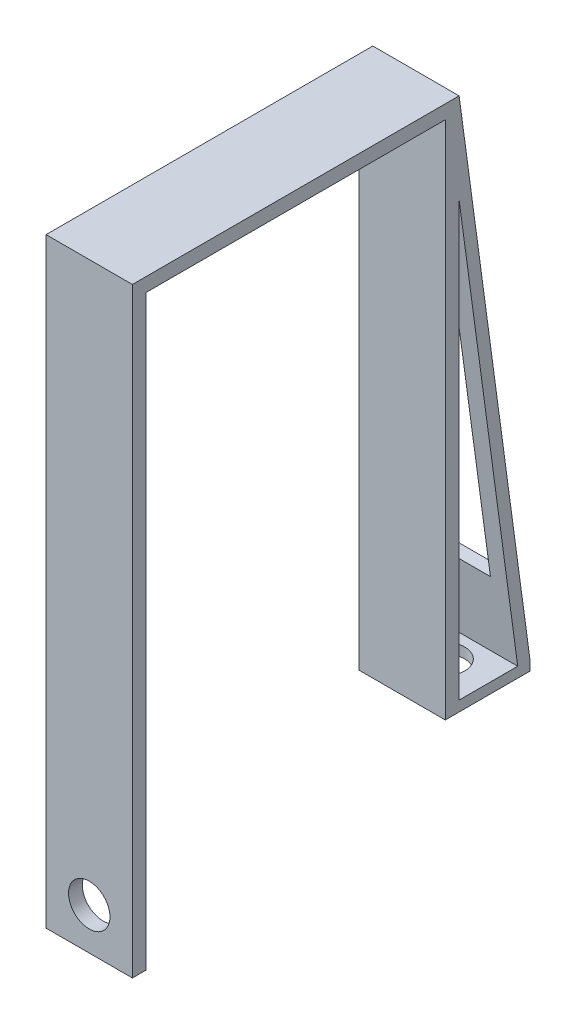
SolidWorks part; units mm, degrees
ref_plane "Front Plane" through (0, 0, 0) normal (0, 0, 1) x (1, 0, 0)
ref_plane "Top Plane" through (0, 0, 0) normal (0, 1, 0) x (1, 0, 0)
ref_plane "Right Plane" through (0, 0, 0) normal (1, 0, 0) x (0, 0, -1)
sketch "Sketch2" plane through (0, 0, 0) normal (0, 0, 1) x (1, 0, 0)
  line L1 (-123.2034, -97.4239) -> (-98.2034, -97.4239)
  line L2 (-123.2034, -97.4239) -> (-123.2034, 72.5761)
  line L3 (-123.2034, 72.5761) -> (-98.2034, 72.5761)
  line L4 (-98.2034, -97.4239) -> (-98.2034, 72.5761)
  circle A2 centre (-110.7034, -85.3746) radius 6
  dimension "D1" = 170
  dimension "D2" = 25
extrude "Boss-Extrude1" add sketch "Sketch2" along normal blind 4
sketch "Sketch3" plane through (0, 72.5761, 0) normal (0, 1, 0) x (1, 0, 0)
  line L13 (-123.2034, -4) -> (-98.2034, -4)
  line L14 (-123.2034, -4) -> (-123.2034, 86.65)
  line L15 (-123.2034, 86.65) -> (-98.2034, 86.65)
  line L16 (-98.2034, -4) -> (-98.2034, 86.65)
  dimension "D1" = 25
  dimension "D2" = 90.65
extrude "Boss-Extrude2" add sketch "Sketch3" along normal blind 4
sketch "Sketch5" plane through (0, 0, -86.65) normal (0, 0, -1) x (-1, 0, 0)
  line L9 (98.2034, -78.0239) -> (123.2034, -78.0239)
  line L10 (98.2034, -78.0239) -> (98.2034, 76.5761)
  line L11 (98.2034, 76.5761) -> (123.2034, 76.5761)
  line L12 (123.2034, -78.0239) -> (123.2034, 76.5761)
  dimension "D1" = 25
  dimension "D2" = 154.6
extrude "Boss-Extrude3" add sketch "Sketch5" along normal blind 4 contours L10 L9 L12 L11
sketch "Sketch6" plane through (-123.2034, 0, 0) normal (-1, 0, 0) x (0, 0, 1)
  line L1 (-90.65, -78.0239) -> (-111.1634, -78.0239)
  line L2 (-90.65, -78.0239) -> (-90.65, -75.0239)
  line L3 (-90.65, -75.0239) -> (-111.1634, -75.0239)
  line L4 (-111.1634, -78.0239) -> (-111.1634, -75.0239)
  dimension "D1" = 3
extrude "Boss-Extrude4" add sketch "Sketch6" along direction (-1, 0, 0) on the side against the normal up to surface (25 mm away) up to face at (-98.2034, -6.5739, -43.325)
sketch "Sketch8" plane through (-98.2034, 0, 0) normal (1, 0, 0) x (0, 0, -1)
  line L0 (90.65, 76.5761) -> (111.1634, -75.0239)
  line L1 (111.1634, -75.0239) -> (107.6315, -75.0239)
  line L2 (111.1634, -75.0239) -> (90.65, -75.0239) construction
  line L3 (107.6315, -75.0239) -> (90.65, 50.4744)
  line L4 (90.65, 50.4744) -> (90.65, 76.5761)
  line L5 (90.65, -75.0239) -> (90.65, 76.5761) construction
  dimension "D1" = 3.5
extrude "Boss-Extrude6" add sketch "Sketch8" against normal up to surface (25 mm away) up to face at (-123.2034, -20.2639, -56.8927)
sketch "Sketch12" plane through (0, -78.0239, 0) normal (0, -1, 0) x (-1, 0, 0)
  circle A1 centre (110.7034, 98.7817) radius 6
extrude "Cut-Extrude2" cut sketch "Sketch12" against normal blind 4
sketch "Sketch13" plane through (0, 12.9531, -95.7271) normal (0, -0.1341, 0.991) x (1, 0, 0)
  line L0 (-98.2034, 37.8632) -> (-98.2034, -88.7787) construction
  line L1 (-118.2034, -67.1416) -> (-103.2034, -67.1416)
  line L2 (-118.2034, -67.1416) -> (-118.2034, 38.2172)
  line L3 (-118.2034, 38.2172) -> (-103.2034, 38.2172)
  line L4 (-103.2034, -67.1416) -> (-103.2034, 38.2172)
  line L5 (-123.2034, -88.7787) -> (-123.2034, 37.8632) construction
  dimension "D1" = 5
  dimension "D2" = 5
extrude "Cut-Extrude3" cut sketch "Sketch13" against normal blind 10
